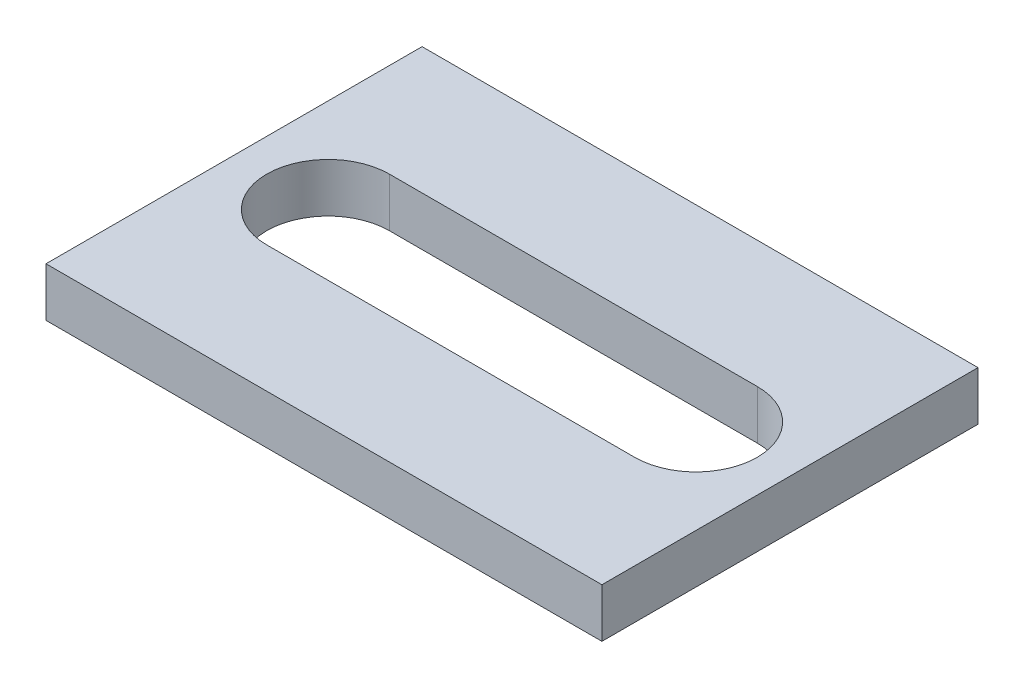
SolidWorks part; units mm, degrees
material "Pine"
ref_plane "Front Plane" through (0, 0, 0) normal (0, 0, 1) x (1, 0, 0)
ref_plane "Top Plane" through (0, 0, 0) normal (0, 1, 0) x (1, 0, 0)
ref_plane "Right Plane" through (0, 0, 0) normal (1, 0, 0) x (0, 0, -1)
sketch "Sketch2" plane through (0, 0, 0) normal (0, 1, 0) x (1, 0, 0)
  line L4 (23, 46) -> (113, 46) construction
  line L5 (0, 0) -> (136, 0)
  line L6 (0, 0) -> (0, 92)
  line L7 (0, 92) -> (136, 92)
  line L8 (136, 0) -> (136, 92)
  line L9 (23, 61) -> (113, 61)
  line L10 (23, 31) -> (113, 31)
  arc A0 (23, 61) -> (23, 31) centre (23, 46) ccw
  arc A1 (113, 31) -> (113, 61) centre (113, 46) ccw
  point P7 (68, 46)
  dimension "D3" = 46
  dimension "D5" = 15
  dimension "D1" = 92
  dimension "D2" = 136
  dimension "D4" = 23
  dimension "D6" = 90
extrude "Boss-Extrude1" add sketch "Sketch2" along normal blind 12 contours L7 L8 L5 L6
extrude "Cut-Extrude1" cut sketch "Sketch2<3>" along normal up to surface (12 mm away) contours A0 L10 A1 L9 up to face at (68, 12, -46)
sketch "Sketch2<3>" plane through (0, 0, 0) normal (0, 1, 0) x (1, 0, 0) same geometry as "Sketch2"
equation "\"LENGTH\" = 900mm"
equation "\"PLY\"= 12mm"
equation "\"D1@Boss-Extrude1\"=\"PLY\""
